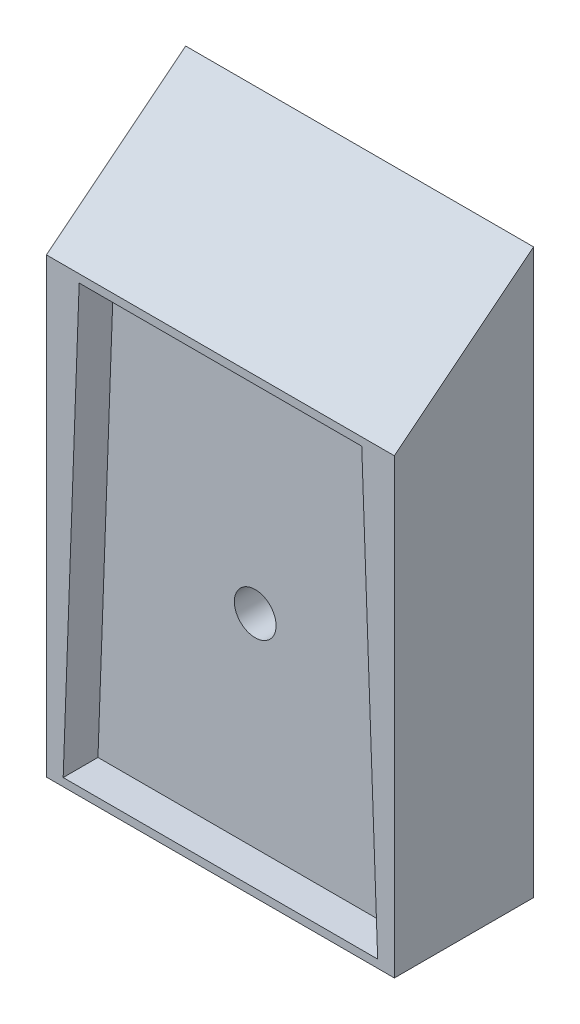
SolidWorks part; units mm, degrees
ref_plane "Přední rovina" through (0, 0, 0) normal (0, 0, 1) x (1, 0, 0)
ref_plane "Horní rovina" through (0, 0, 0) normal (0, 1, 0) x (1, 0, 0)
ref_plane "Pravá rovina" through (0, 0, 0) normal (1, 0, 0) x (0, 0, -1)
sketch "Skica1" plane through (0, 0, 0) normal (0, 0, 1) x (1, 0, 0)
  line L0 (-25, 32.5) -> (25, 32.5)
  line L1 (-25, 32.5) -> (-25, -32.5)
  line L2 (-25, -32.5) -> (25, -32.5)
  line L3 (25, 32.5) -> (25, -32.5)
  dimension "D1" = 50
  dimension "D2" = 65
extrude "Přidat vysunutím1" add sketch "Skica1" along normal blind 20
sketch "Skica3" plane through (25, 0, 0) normal (1, 0, 0) x (0, 0, -1)
  line L0 (0, 32.5) -> (0, 48.5)
  line L1 (0, 48.5) -> (-20, 32.5)
  line L6 (0, -32.5) -> (0, 32.5)
  line L7 (0, 32.5) -> (-20, 32.5)
  line L8 (-20, 32.5) -> (-20, -32.5)
  line L9 (-20, -32.5) -> (0, -32.5)
  line L11 (0, 32.5) -> (-20, 32.5)
  dimension "D1" = 16
  dimension "D2" = 20
  dimension "D3" = 0
extrude "Přidat vysunutím2" add sketch "Skica3" against normal through all
sketch "Skica5" plane through (0, 0, 20) normal (0, 0, 1) x (1, 0, 0)
  line L0 (-20.3, 31.35) -> (20.31, 31.35)
  line L2 (-25, -32.5) -> (25, -32.5) construction
  line L3 (20.31, 31.35) -> (22.6, -31.35)
  line L5 (-20.3, 31.35) -> (20.31, 31.35) construction
  line L7 (22.6, -31.35) -> (-22.6, -31.35)
  line L11 (-20.3, 31.35) -> (-22.6, -31.35)
  line L12 (-25, 32.5) -> (-25, -32.5) construction
  dimension "D1" = 45.2
  dimension "D2" = 40.61
  dimension "D3" = 1.15
  dimension "D4" = 4.7
  dimension "D5" = 62.7
  dimension "D6" = 2.4
extrude "Odebrat vysunutím1" cut sketch "Skica5" against normal offset from surface (5 mm away) 5 up to face at (0, 0, 20)
sketch "Skica6" plane through (0, 0, 15) normal (0, 0, 1) x (1, 0, 0)
  line L3 (22.6, -31.35) -> (-22.6, -31.35) construction
  circle A0 centre (0, -2.15) radius 3
  dimension "D2" = 6
  dimension "D1" = 29.2
sketch "Skica7" plane through (0, 0, 0) normal (0, 0, -1) x (-1, 0, 0)
  circle A2 centre (0, -2.15) radius 7.5
  dimension "D1" = 15
sketch "Skica8" plane through (0, 0, 0) normal (0, 0, -1) x (-1, 0, 0)
  line L0 (-25, 15.3) -> (25, 15.3) construction
  line L1 (-25, -32.5) -> (-25, 48.5) construction
  line L2 (25, 48.5) -> (25, -32.5) construction
  line L3 (25, 48.5) -> (-25, 48.5) construction
  line L4 (0, 15.3) -> (0, 48.5) construction
  line L5 (0, 31.9) -> (25, 31.9) construction
  line L6 (0, 31.9) -> (-25, 31.9) construction
  circle A0 centre (7.149, 24.75) radius 2.425
  circle A1 centre (-7.149, 24.75) radius 2.425
  circle A2 centre (7.149, 39.05) radius 2.425
  circle A3 centre (-7.149, 39.05) radius 2.425
  dimension "D2" = 4.85
  dimension "D3" = 7.15
  dimension "D4" = 7.149
  dimension "D1" = 33.2
extrude "Odebrat vysunutím4" cut sketch "Skica8" against normal blind 8.5
extrude "Odebrat vysunutím7" cut sketch "Skica6" against normal blind 10
extrude "Odebrat vysunutím8" cut sketch "Skica7" against normal blind 10
sketch "Skica9" plane through (0, 0, 10) normal (0, 0, -1) x (-1, 0, 0)
  line L0 (-3, -2.15) -> (-3, -9.0239)
  line L5 (-3, -2.15) -> (-3, 4.7239)
  line L6 (3, -2.15) -> (3, -9.0239)
  line L7 (3, -2.15) -> (3, 4.7239)
  circle A2 centre (0, -2.15) radius 3 construction
  circle A3 centre (0, -2.15) radius 7.5 construction
  arc A4 (-3, -9.0239) -> (-3, 4.7239) centre (0, -2.15) cw
  arc A5 (3, 4.7239) -> (3, -9.0239) centre (0, -2.15) cw
  dimension "D3" = 7.5
  dimension "D1" = 3
  dimension "D2" = 3
extrude "Přidat vysunutím3" add sketch "Skica9" along normal blind 0.2
sketch "Skica15" plane through (0, 0, 10) normal (0, 0, -1) x (-1, 0, 0)
  line L0 (0, 0.85) -> (6.8739, 0.85)
  line L1 (0, 0.85) -> (-6.8739, 0.85)
  line L2 (0, -2.15) -> (3, -2.15) construction
  line L3 (3, 4.7239) -> (3, -2.15) construction
  line L4 (0, -5.15) -> (-6.8739, -5.15)
  line L5 (0, -5.15) -> (6.8739, -5.15)
  arc A0 (3, -2.15) -> (-3, -2.15) centre (0, -2.15) ccw construction
  arc A1 (3, -9.0239) -> (3, 4.7239) centre (0, -2.15) ccw construction
  circle A2 centre (0, -2.15) radius 7.5 construction
  arc A3 (-6.8739, 0.85) -> (6.8739, 0.85) centre (0, -2.15) cw
  arc A4 (-3, -2.15) -> (3, -2.15) centre (0, -2.15) ccw construction
  arc A5 (-6.8739, -5.15) -> (6.8739, -5.15) centre (0, -2.15) ccw
extrude "Přidat vysunutím5" add sketch "Skica15" along normal blind 0.4
